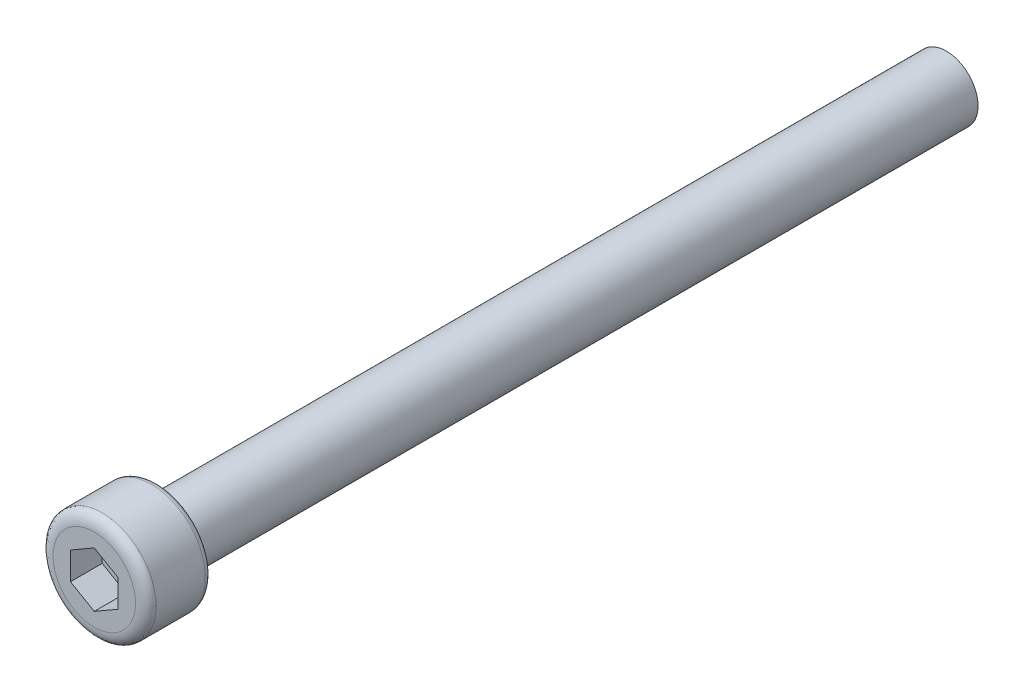
SolidWorks part; units mm, degrees
ref_plane "前视基准面" through (0, 0, 0) normal (0, 0, 1) x (1, 0, 0)
ref_plane "上视基准面" through (0, 0, 0) normal (0, 1, 0) x (1, 0, 0)
ref_plane "右视基准面" through (0, 0, 0) normal (1, 0, 0) x (0, 0, -1)
sketch "草图2" plane through (0, 0, 0) normal (1, 0, 0) x (0, 0, -1)
  line L0 (-27, 0) -> (-27, 3.4)
  line L1 (-27, 3.4) -> (-23, 3.4)
  line L2 (-23, 3.4) -> (-23, 2)
  line L3 (-23, 2) -> (27, 2)
  line L4 (27, 2) -> (27, 0)
  line L5 (27, 0) -> (-27, 0)
  dimension "D1" = 50
  dimension "D2" = 3.4
  dimension "D3" = 2
  dimension "D4" = 4
revolve "旋转1" add sketch "草图2" angle 360 about L5
chamfer "倒角1" distance 0.3 angle 60 1 edges at (-2, 0, -27) first distance on face at (-2, 0, 23)
fillet "圆角1" radius 0.4 1 edges at (-3.4, 0, 23)
fillet "圆角2" radius 0.8 1 edges at (-3.4, 0, 27) second distance 0.5 first distance on face at (-3.4, 0, 27)
sketch "草图3" plane through (0, 0, 27) normal (0, 0, 1) x (1, 0, 0)
  line L1 (0, 1.7321) -> (-1.5, 0.866)
  line L2 (-1.5, 0.866) -> (-1.5, -0.866)
  line L3 (-1.5, -0.866) -> (0, -1.7321)
  line L4 (0, -1.7321) -> (1.5, -0.866)
  line L5 (1.5, -0.866) -> (1.5, 0.866)
  line L6 (1.5, 0.866) -> (0, 1.7321)
  circle A0 centre (0, 0) radius 1.5 construction
  dimension "D1" = 3
extrude "切除-拉伸1" cut sketch "草图3" against normal blind 2
